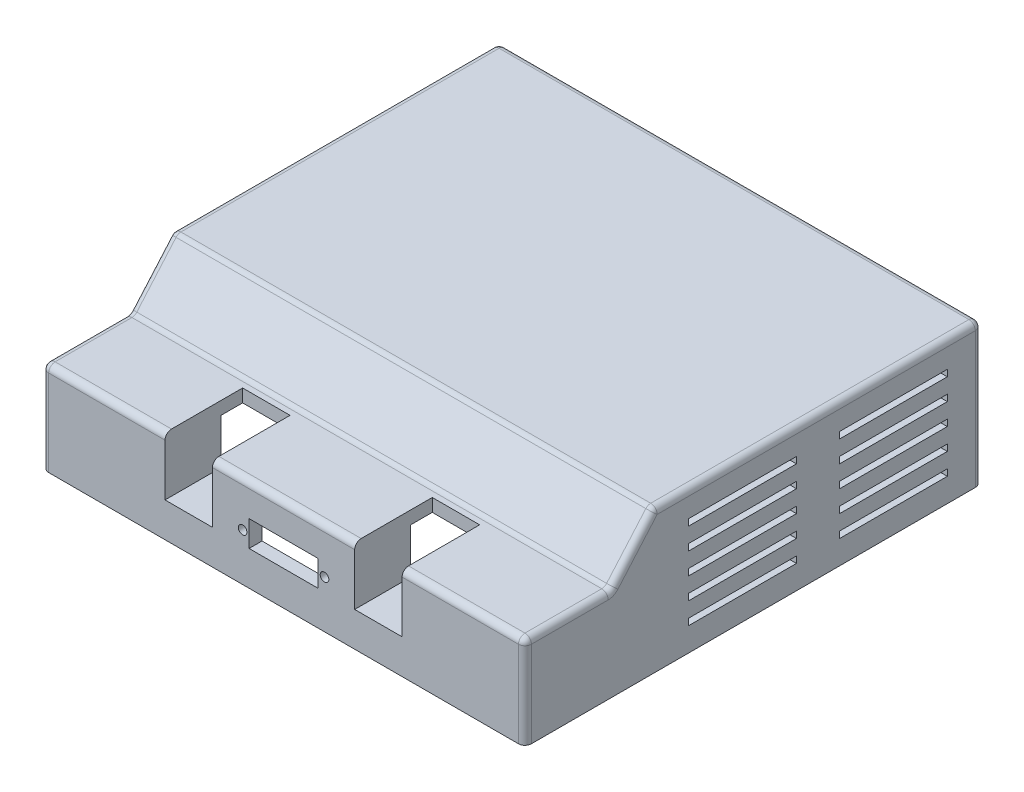
SolidWorks part; units mm, degrees
other "Markup1"
sketch "Sketch15" plane through (-54, 3, -54) normal (0, 1, 0) x (1, 0, 0)
ref_plane "Front Plane" through (0, 0, 0) normal (0, 0, 1) x (1, 0, 0)
ref_plane "Top Plane" through (0, 0, 0) normal (0, 1, 0) x (1, 0, 0)
ref_plane "Right Plane" through (0, 0, 0) normal (1, 0, 0) x (0, 0, -1)
sketch "Sketch1" plane through (0, 0, 0) normal (0, 1, 0) x (1, 0, 0)
  line L1 (-56, -53) -> (56, -53)
  line L2 (-56, -53) -> (-56, 53)
  line L3 (-56, 53) -> (56, 53)
  line L4 (56, -53) -> (56, 53)
  line L5 (-56, -53) -> (56, 53) construction
  line L6 (-56, 53) -> (56, -53) construction
  point P0 (0, 0)
  dimension "D1" = 112
  dimension "D2" = 106
extrude "Boss-Extrude1" add sketch "Sketch1" along normal blind 3
sketch "Sketch3" plane through (0, 0, 0) normal (0, -1, 0) x (1, 0, 0)
  line L0 (56, 53) -> (56, -53) construction
  line L5 (-56, -53) -> (56, -53)
  line L6 (-56, -53) -> (-56, 53)
  line L11 (-56, 53) -> (56, 53)
  line L12 (56, -53) -> (56, 53)
  line L13 (-56, -53) -> (56, 53) construction
  line L14 (-56, 53) -> (56, -53) construction
  line L15 (0, -53) -> (0, 53) construction
  line L16 (-52.8302, -50) -> (52.8302, -50)
  line L17 (-52.8302, -50) -> (-52.8302, 50)
  line L18 (-52.8302, 50) -> (52.8302, 50)
  line L19 (52.8302, -50) -> (52.8302, 50)
  line L20 (-52.8302, -50) -> (52.8302, 50) construction
  line L21 (-52.8302, 50) -> (52.8302, -50) construction
  line L22 (-56, 0) -> (56, 0) construction
  arc A2 (-52.8302, 41.4262) -> (-44.381, 50) centre (-56, 53) ccw
  arc A3 (52.8302, 41.4262) -> (44.381, 50) centre (56, 53) cw
  arc A4 (52.8302, -41.4262) -> (44.381, -50) centre (56, -53) ccw
  arc A5 (-52.8302, -41.4262) -> (-44.381, -50) centre (-56, -53) cw
  point P0 (0, 0)
  point P1 (0, 0)
  point P7 (0, 0)
  point P11 (0, 0)
  line M12 (56, -53) -> (56, 53)
  line M13 (56, 53) -> (-56, 53)
  line M14 (-56, 53) -> (-56, -53)
  line M15 (-56, -53) -> (56, -53)
  dimension "D2" = 3
  dimension "D1" = 106
extrude "Boss-Extrude2" add sketch "Sketch3" along normal blind 30 contours M15 M12 M13 M14 | L17 A2 L18 | A5 L17 L16 | L19 A4 L16 | A3 L19 L18 region at (-54.4579, 0, 0) region at (-49.5145, 0, -46.639) region at (49.5145, 0, -46.639) region at (-49.5145, 0, 46.639) region at (49.5145, 0, 46.639)
sketch "Sketch4" plane through (0, -30, 0) normal (0, -1, 0) x (1, 0, 0)
  line L1 (-51.5, -48.5) -> (51.5, -48.5)
  line L2 (-51.5, -48.5) -> (-51.5, 48.5)
  line L3 (-51.5, 48.5) -> (51.5, 48.5)
  line L4 (51.5, -48.5) -> (51.5, 48.5)
  line L5 (-51.5, -48.5) -> (51.5, 48.5) construction
  line L6 (-51.5, 48.5) -> (51.5, -48.5) construction
  circle A0 centre (-51.5, 48.5) radius 1.5
  circle A1 centre (-51.5, -48.5) radius 1.5
  circle A2 centre (51.5, -48.5) radius 1.5
  circle A3 centre (51.5, 48.5) radius 1.5
  point P0 (0, 0)
  dimension "D1" = 103
  dimension "D2" = 97
extrude "Cut-Extrude1" cut sketch "Sketch4" against normal blind 15 contours L3 A0 L2 | L2 A0 L3 | L2 A1 L1 | L1 A1 L2 | L1 A2 L4 | L4 A2 L1 | L4 A3 L3 | L3 A3 L4 region at (-50.8634, -30, -47.8634) region at (-51.7122, -30, -48.7122) region at (50.8634, -30, -47.8634) region at (51.7122, -30, -48.7122) region at (-51.7122, -30, 48.7122) region at (-50.8634, -30, 47.8634) region at (50.8634, -30, 47.8634) region at (51.7122, -30, 48.7122)
sketch "Sketch5" plane through (0, 0, 53) normal (0, 0, 1) x (1, 0, 0)
  line L0 (-56, -13.5) -> (56, -13.5) construction
  line L1 (-56, 3) -> (-56, -30) construction
  line L2 (56, 3) -> (56, -30) construction
  line L3 (0, -30) -> (0, 3) construction
  line L4 (56, -30) -> (-56, -30) construction
  line L5 (-56, 3) -> (56, 3) construction
  line L6 (-9.4992, -19) -> (9.4992, -19) construction
  line L7 (-8, -22) -> (8, -22)
  line L8 (-8, -22) -> (-8, -16)
  line L9 (-8, -16) -> (8, -16)
  line L10 (8, -22) -> (8, -16)
  line L11 (-8, -22) -> (8, -16) construction
  line L12 (-8, -16) -> (8, -22) construction
  circle A0 centre (9.5, -19) radius 1
  circle A1 centre (-9.5, -19) radius 1
  point P12 (0, -19)
  point P21 (0, 0)
  point P22 (0, 0)
  point P23 (0, 0)
  point P26 (0, 0)
  point P27 (0, 0)
  point P28 (0, 0)
  point P29 (0, 0)
  point P30 (0, 0)
  point P31 (0, 0)
  point P32 (0, 0)
  point P33 (0, 0)
  dimension "D3" = 9.5
  dimension "D1" = 16
  dimension "D2" = 6
  dimension "D4" = 9.5
  dimension "D5" = 11
extrude "Cut-Extrude2" cut sketch "Sketch5" against normal blind 3
sketch "Sketch7" plane through (56, 0, 0) normal (1, 0, 0) x (0, 0, -1)
  line L1 (-53, 3) -> (-23, 3)
  line L2 (-53, 3) -> (-53, -11.5)
  line L3 (-53, -11.5) -> (-23, -11.5)
  line L4 (-23, 3) -> (-23, -11.5)
  dimension "D1" = 14.5
  dimension "D2" = 30
extrude "Cut-Extrude4" cut sketch "Sketch7" against normal blind 112
sketch "Sketch9" plane through (0, -11.5, 0) normal (0, 1, 0) x (1, 0, 0)
  line L0 (56, -53) -> (56, -23) construction
  line L1 (-56, -53) -> (56, -53)
  line L2 (-56, -53) -> (-56, -33)
  line L3 (-56, -33) -> (56, -33)
  line L4 (56, -53) -> (56, -33)
  line L5 (-56, 53) -> (-56, -23) construction
  line L6 (-56, -53) -> (56, -53) construction
  point P5 (0, 0)
  point P6 (0, 0)
  dimension "D1" = 20
extrude "Boss-Extrude3" add sketch "Sketch9" along normal blind 3
sketch "Sketch10" plane through (0, -8.5, 0) normal (0, 1, 0) x (1, 0, 0)
  line L0 (0, 37.5) -> (0, -33) construction
  line L1 (-37.5, -37.5) -> (37.5, -37.5)
  line L2 (-37.5, -37.5) -> (-37.5, 37.5)
  line L3 (-37.5, 37.5) -> (37.5, 37.5)
  line L4 (37.5, -37.5) -> (37.5, 37.5)
  line L5 (-37.5, -37.5) -> (37.5, 37.5) construction
  line L6 (-37.5, 37.5) -> (37.5, -37.5) construction
  line L7 (-47.5, -47.5) -> (47.5, -47.5)
  line L8 (-47.5, -47.5) -> (-47.5, 47.5)
  line L9 (-47.5, 47.5) -> (47.5, 47.5)
  line L10 (47.5, -47.5) -> (47.5, 47.5)
  line L11 (-47.5, -47.5) -> (47.5, 47.5) construction
  line L12 (-47.5, 47.5) -> (47.5, -47.5) construction
  line L13 (56, -33) -> (-56, -33) construction
  line L14 (-16.5, -35) -> (-27.5, -35)
  line L15 (16.5, -53) -> (27.5, -53)
  line L16 (16.5, -53) -> (16.5, -35)
  line L17 (16.5, -35) -> (27.5, -35)
  line L18 (27.5, -53) -> (27.5, -35)
  line L19 (-27.5, -53) -> (-27.5, -35)
  line L20 (-16.5, -53) -> (-27.5, -53)
  line L21 (-16.5, -53) -> (-16.5, -35)
  line L22 (-56, -53) -> (56, -53) construction
  point P0 (0, 0)
  point P6 (0, 0)
  point P23 (0, 0)
  point P24 (0, 0)
  point P25 (0, 0)
  point P26 (0, 0)
  point P27 (-17.5, -56)
  dimension "D1" = 75
  dimension "D2" = 75
  dimension "D3" = 95
  dimension "D4" = 95
  dimension "D5" = 20
  dimension "D6" = 11
  dimension "D7" = 18
extrude "Cut-Extrude5" cut sketch "Sketch10" against normal blind 13.5 contours L7 L18 L17 L16 | L7 L21 L14 L19 | L14 L19 L20 L21 | L16 L15 L18 L17 region at (-22, -8.5, 42.5) region at (22, -8.5, 42.5)
sketch "Sketch11" plane through (56, 0, 0) normal (1, 0, 0) x (0, 0, -1)
  line L0 (-33, -8.5) -> (-23, 3)
  line L1 (-33, -8.5) -> (-33, -11.5)
  line L2 (-33, -11.5) -> (-23, 0)
  line L3 (-23, 0) -> (-23, 3)
  point P4 (-83.5954, 17.7048)
extrude "Boss-Extrude4" add sketch "Sketch11" against normal blind 112
sketch "Sketch13" plane through (56, 0, 0) normal (1, 0, 0) x (0, 0, -1)
  line L0 (-33, -11.5) -> (-23, 0)
  line L1 (-23, 0) -> (-23, -11.5)
  line L2 (-23, -11.5) -> (-33, -11.5)
extrude "Boss-Extrude5" add sketch "Sketch13" against normal blind 3
sketch "Sketch14" plane through (-56, 0, 0) normal (-1, 0, 0) x (0, 0, 1)
  line L0 (23, 0) -> (23, -11.5)
  line L1 (23, -11.5) -> (33, -11.5)
  line L2 (33, -11.5) -> (23, 0)
extrude "Boss-Extrude6" add sketch "Sketch14" against normal blind 3
sketch "Sketch16" plane through (0, 0, 53) normal (0, 0, 1) x (1, 0, 0)
  line L0 (-56, -18.5) -> (56, -18.5) construction
  line L1 (-56, -8.5) -> (-56, -30) construction
  line L2 (56, -8.5) -> (56, -30) construction
  line L3 (-22.5, -18.5) -> (22.5, -18.5)
  line L4 (56, -30) -> (-56, -30) construction
  line L5 (-27.5, -21.5) -> (-17.5, -21.5)
  line L6 (-27.5, -21.5) -> (-27.5, -15.5)
  line L7 (-27.5, -15.5) -> (-17.5, -15.5)
  line L8 (-17.5, -21.5) -> (-17.5, -15.5)
  line L9 (-27.5, -21.5) -> (-17.5, -15.5) construction
  line L10 (-27.5, -15.5) -> (-17.5, -21.5) construction
  line L11 (17.5, -21.5) -> (27.5, -21.5)
  line L12 (17.5, -21.5) -> (17.5, -15.5)
  line L13 (17.5, -15.5) -> (27.5, -15.5)
  line L14 (27.5, -21.5) -> (27.5, -15.5)
  line L15 (17.5, -21.5) -> (27.5, -15.5) construction
  line L16 (17.5, -15.5) -> (27.5, -21.5) construction
  point P9 (0, -18.5)
  dimension "D1" = 45
  dimension "D2" = 6
  dimension "D3" = 10
  dimension "D4" = 10
  dimension "D5" = 6
  dimension "D6" = 8.5
sketch "Sketch19" plane through (0, 0, -53) normal (0, 0, -1) x (-1, 0, 0)
  line L0 (56, -30) -> (-56, -30) construction
  line L1 (18.5, -21.5) -> (27.5, -21.5)
  line L2 (18.5, -21.5) -> (18.5, -11.5)
  line L3 (18.5, -11.5) -> (27.5, -11.5)
  line L4 (27.5, -21.5) -> (27.5, -11.5)
  line L5 (56, 3) -> (56, -30) construction
  dimension "D1" = 9
  dimension "D2" = 10
  dimension "D3" = 8.5
  dimension "D4" = 28.5
extrude "Cut-Extrude7" cut sketch "Sketch19" against normal blind 3
sketch "Sketch20" plane through (0, 0, -53) normal (0, 0, 1) x (1, 0, 0)
  line L0 (-23, -21.5) -> (-23, -11.5) construction
  line L1 (-18.5, -21.5) -> (-27.5, -21.5) construction
  line L2 (-27.5, -11.5) -> (-18.5, -11.5) construction
  line L3 (-27.5, -16.5) -> (-18.5, -16.5) construction
  line L4 (-27.5, -21.5) -> (-27.5, -11.5) construction
  line L5 (-18.5, -11.5) -> (-18.5, -21.5) construction
  line L7 (-27.5, -21.5) -> (-18.5, -21.5)
  line L8 (-27.5, -21.5) -> (-27.5, -11.5)
  line L9 (-27.5, -11.5) -> (-18.5, -11.5)
  line L10 (-18.5, -21.5) -> (-18.5, -11.5)
  line L11 (-27.5, -21.5) -> (-18.5, -11.5) construction
  line L12 (-27.5, -11.5) -> (-18.5, -21.5) construction
  line L13 (-29, -23) -> (-17, -23)
  line L14 (-29, -23) -> (-29, -10)
  line L15 (-29, -10) -> (-17, -10)
  line L16 (-17, -23) -> (-17, -10)
  line L17 (-29, -23) -> (-17, -10) construction
  line L18 (-29, -10) -> (-17, -23) construction
  point P12 (-23, -16.5)
  point P18 (-23, -16.5)
  dimension "D1" = 1.5
  dimension "D2" = 1.5
extrude "Boss-Extrude8" add sketch "Sketch20" along normal blind 3
sketch "Sketch21" plane through (0, 0, -53) normal (0, 0, -1) x (-1, 0, 0)
  line L0 (-28.5, -19.25) -> (-13.5, -19.25)
  line L1 (-28.5, -19.25) -> (-28.5, -10.75)
  line L2 (-28.5, -10.75) -> (-13.5, -10.75)
  line L3 (-13.5, -19.25) -> (-13.5, -10.75)
  line L4 (-28.5, -19.25) -> (-13.5, -10.75) construction
  line L5 (-28.5, -10.75) -> (-13.5, -19.25) construction
  line L6 (-56, 3) -> (-56, -30) construction
  line L8 (56, -30) -> (-56, -30) construction
  point P0 (-21, -15)
  dimension "D1" = 35
  dimension "D2" = 15
  dimension "D3" = 8.5
  dimension "D4" = 15
extrude "Cut-Extrude8" cut sketch "Sketch21" against normal blind 3
sketch "Sketch23" plane through (56, 0, 0) normal (1, 0, 0) x (0, 0, -1)
  line L0 (15, 3) -> (15, -30) construction
  line L1 (-23, 3) -> (53, 3) construction
  line L2 (53, -30) -> (-53, -30) construction
  line L3 (20, -8) -> (45, -8)
  line L4 (20, -3) -> (45, -3)
  line L5 (20, -3) -> (20, -4.5)
  line L6 (20, -4.5) -> (45, -4.5)
  line L7 (45, -3) -> (45, -4.5)
  line L8 (20, -8) -> (20, -9.5)
  line L9 (20, -9.5) -> (45, -9.5)
  line L10 (45, -8) -> (45, -9.5)
  line L11 (20, -13) -> (45, -13)
  line L12 (20, -13) -> (20, -14.5)
  line L13 (20, -14.5) -> (45, -14.5)
  line L14 (45, -13) -> (45, -14.5)
  line L15 (20, -18) -> (45, -18)
  line L16 (20, -18) -> (20, -19.5)
  line L17 (20, -19.5) -> (45, -19.5)
  line L18 (45, -18) -> (45, -19.5)
  line L19 (20, -23) -> (45, -23)
  line L20 (20, -23) -> (20, -24.5)
  line L21 (20, -24.5) -> (45, -24.5)
  line L22 (45, -23) -> (45, -24.5)
  line L23 (10, -23) -> (10, -24.5)
  line L24 (10, -24.5) -> (-15, -24.5)
  line L25 (-15, -23) -> (-15, -24.5)
  line L26 (10, -23) -> (-15, -23)
  line L27 (10, -18) -> (10, -19.5)
  line L28 (10, -19.5) -> (-15, -19.5)
  line L29 (-15, -18) -> (-15, -19.5)
  line L30 (10, -18) -> (-15, -18)
  line L31 (10, -13) -> (10, -14.5)
  line L32 (10, -14.5) -> (-15, -14.5)
  line L33 (-15, -13) -> (-15, -14.5)
  line L34 (10, -13) -> (-15, -13)
  line L35 (10, -8) -> (10, -9.5)
  line L36 (10, -9.5) -> (-15, -9.5)
  line L37 (-15, -8) -> (-15, -9.5)
  line L38 (10, -8) -> (-15, -8)
  line L39 (10, -4.5) -> (-15, -4.5)
  line L40 (-15, -3) -> (-15, -4.5)
  line L41 (10, -3) -> (-15, -3)
  line L42 (10, -3) -> (10, -4.5)
  dimension "D1" = 25
  dimension "D2" = 1.5
  dimension "D3" = 6
  dimension "D4" = 5
  dimension "D5" = 5
  dimension "D6" = 5
  dimension "D7" = 5
  dimension "D8" = 5
  dimension "D9" = 3.5
  dimension "D10" = 3.5
  dimension "D11" = 3.5
  dimension "D12" = 3.5
extrude "Cut-Extrude9" cut sketch "Sketch23" against normal blind 3
sketch "Sketch24" plane through (-56, 0, 0) normal (-1, 0, 0) x (0, 0, 1)
  line L0 (-15, 3) -> (-15, -30) construction
  line L1 (-53, 3) -> (23, 3) construction
  line L2 (53, -30) -> (-53, -30) construction
  line L3 (-15, 3) -> (-15, -30) construction
  line L4 (-10, -6.5) -> (15, -6.5)
  line L5 (-10, -4.5) -> (15, -4.5)
  line L6 (-10, -4.5) -> (-10, -3)
  line L7 (-10, -3) -> (15, -3)
  line L8 (15, -4.5) -> (15, -3)
  line L9 (-10, -6.5) -> (-10, -8)
  line L10 (-10, -8) -> (15, -8)
  line L11 (15, -6.5) -> (15, -8)
  line L12 (-10, -11.5) -> (15, -11.5)
  line L13 (-10, -11.5) -> (-10, -13)
  line L14 (-10, -13) -> (15, -13)
  line L15 (15, -11.5) -> (15, -13)
  line L16 (-10, -16.5) -> (15, -16.5)
  line L17 (-10, -16.5) -> (-10, -18)
  line L18 (-10, -18) -> (15, -18)
  line L19 (15, -16.5) -> (15, -18)
  line L20 (-10, -21.5) -> (15, -21.5)
  line L21 (-10, -21.5) -> (-10, -23)
  line L22 (-10, -23) -> (15, -23)
  line L23 (15, -21.5) -> (15, -23)
  line L24 (-20, -21.5) -> (-20, -23)
  line L25 (-20, -23) -> (-45, -23)
  line L26 (-45, -21.5) -> (-45, -23)
  line L27 (-20, -21.5) -> (-45, -21.5)
  line L28 (-20, -16.5) -> (-20, -18)
  line L29 (-20, -18) -> (-45, -18)
  line L30 (-45, -16.5) -> (-45, -18)
  line L31 (-20, -16.5) -> (-45, -16.5)
  line L32 (-20, -11.5) -> (-20, -13)
  line L33 (-20, -13) -> (-45, -13)
  line L34 (-45, -11.5) -> (-45, -13)
  line L35 (-20, -11.5) -> (-45, -11.5)
  line L36 (-20, -6.5) -> (-20, -8)
  line L37 (-20, -8) -> (-45, -8)
  line L38 (-45, -6.5) -> (-45, -8)
  line L39 (-20, -6.5) -> (-45, -6.5)
  line L40 (-20, -3) -> (-45, -3)
  line L41 (-45, -4.5) -> (-45, -3)
  line L42 (-20, -4.5) -> (-45, -4.5)
  line L43 (-20, -4.5) -> (-20, -3)
  point P6 (-20, -3.75)
  point P7 (-15, 4.5)
  point P48 (-14.3549, -25)
  point P49 (-20, -12.25)
  dimension "D1" = 5
  dimension "D2" = 5
  dimension "D3" = 5
  dimension "D4" = 5
  dimension "D5" = 5
  dimension "D6" = 3.5
  dimension "D7" = 3.5
  dimension "D8" = 3.5
  dimension "D9" = 3.5
  dimension "D10" = 7.5
  dimension "D11" = 1.5
  dimension "D12" = 25
extrude "Cut-Extrude10" cut sketch "Sketch24" against normal blind 3
fillet "Fillet1" radius 1.5 16 edges at (56, -8.5, 43) (-56, -8.5, 43) (0, -8.5, 33) (-56, -2.75, 28) (56, -2.75, 28) (0, 3, -53) (56, 3, -15) (0, 3, 23) (-56, 3, -15) (-56, -13.5, -53) (56, -13.5, -53) (56, -19.25, 53) (-56, -19.25, 53) (41.75, -8.5, 53) (-41.75, -8.5, 53) (0, -8.5, 53)
sketch "Sketch31" plane through (0, 0, 50) normal (0, 0, -1) x (-1, 0, 0)
  line L0 (-52.8302, -11.5) -> (52.8302, -11.5) construction
  line L1 (-29.5, -11.5) -> (-27.5, -11.5)
  line L2 (-29.5, -11.5) -> (-29.5, -22)
  line L3 (-29.5, -22) -> (-27.5, -22)
  line L4 (-27.5, -11.5) -> (-27.5, -22)
  line L5 (0, -16) -> (0, -22) construction
  line L6 (-29.5, -22) -> (-14.5, -22)
  line L7 (-29.5, -22) -> (-29.5, -23.5)
  line L8 (-29.5, -23.5) -> (-14.5, -23.5)
  line L9 (-14.5, -22) -> (-14.5, -23.5)
  line L10 (-16.5, -22) -> (-14.5, -22)
  line L11 (-16.5, -22) -> (-16.5, -11.5)
  line L12 (-16.5, -11.5) -> (-14.5, -11.5)
  line L13 (-14.5, -22) -> (-14.5, -11.5)
  line L14 (-8, -16) -> (8, -16) construction
  line L15 (8, -22) -> (-8, -22) construction
  line L16 (16.5, -22) -> (16.5, -11.5)
  line L17 (16.5, -11.5) -> (14.5, -11.5)
  line L18 (14.5, -22) -> (14.5, -11.5)
  line L19 (14.5, -22) -> (14.5, -23.5)
  line L20 (29.5, -22) -> (29.5, -23.5)
  line L21 (29.5, -23.5) -> (14.5, -23.5)
  line L22 (27.5, -11.5) -> (27.5, -22)
  line L23 (29.5, -11.5) -> (27.5, -11.5)
  line L24 (29.5, -11.5) -> (29.5, -22)
  line L25 (16.5, -22) -> (27.5, -22)
  line M19 (27.5, -11.5) -> (27.5, -22)
  line M20 (27.5, -22) -> (16.5, -22)
  line M21 (16.5, -22) -> (16.5, -11.5)
  line M22 (16.5, -11.5) -> (-16.5, -11.5)
  line M23 (-16.5, -11.5) -> (-16.5, -22)
  line M24 (-16.5, -22) -> (-27.5, -22)
  line M25 (-27.5, -22) -> (-27.5, -11.5)
  line M26 (-27.5, -11.5) -> (-44.381, -11.5)
  line M30 (44.381, -11.5) -> (27.5, -11.5)
  dimension "D1" = 2
  dimension "D2" = 2
  dimension "D3" = 1.5
extrude "Boss-Extrude16" add sketch "Sketch31" along normal blind 10 contours L2 L3 M25 M26 | L9 L6 L3 L7 L8 M24 | L6 L13 M22 M23 | L24 L18 L19 L21 L20 M30 M19 M20 M21 M22 region at (-15.5, -11.6921, 50) region at (28.5, -16.75, 50) region at (22, -22.75, 50) region at (15.5, -16.75, 50)
